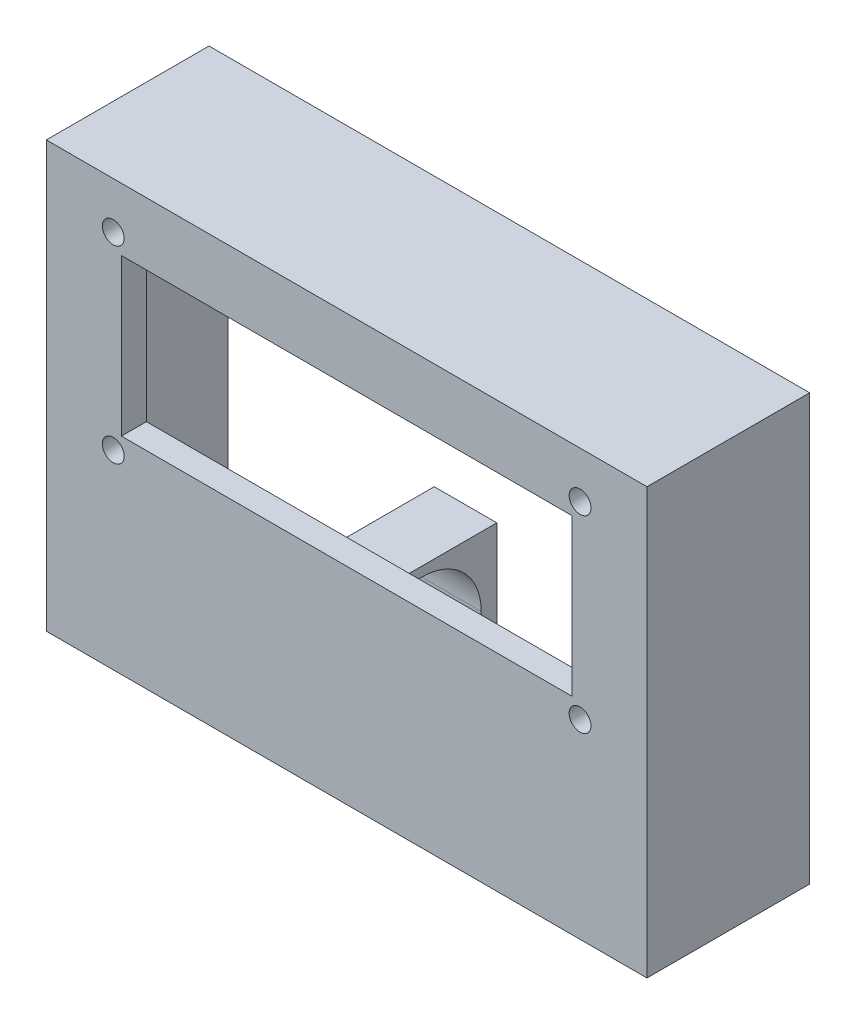
SolidWorks part; units mm, degrees
ref_plane "Plan de face" through (0, 0, 0) normal (0, 0, 1) x (1, 0, 0)
ref_plane "Plan de dessus" through (0, 0, 0) normal (0, 1, 0) x (1, 0, 0)
ref_plane "Plan de droite" through (0, 0, 0) normal (1, 0, 0) x (0, 0, -1)
sketch "Esquisse1" plane through (0, 0, 0) normal (0, 0, 1) x (1, 0, 0)
  line L1 (0, 0) -> (96, 0)
  line L2 (0, 0) -> (0, -68)
  line L3 (0, -68) -> (96, -68)
  line L4 (96, 0) -> (96, -68)
  line L5 (12, -10) -> (84, -10)
  line L6 (12, -10) -> (12, -35)
  line L7 (12, -35) -> (84, -35)
  line L8 (84, -10) -> (84, -35)
  dimension "D1" = 72
  dimension "D2" = 25
  dimension "D3" = 12
  dimension "D4" = 12
  dimension "D5" = 10
  dimension "D6" = 33
extrude "Boss.-Extru.1" add sketch "Esquisse1" along normal blind 4
sketch "Esquisse2" plane through (0, 0, 4) normal (0, 0, 1) x (1, 0, 0)
  line L0 (12, -10) -> (12, -35) construction
  line L2 (84, -35) -> (84, -10) construction
  line L3 (12, -35) -> (84, -35) construction
  line L4 (84, -10) -> (12, -10) construction
  circle A0 centre (85.305, -7.42) radius 1.75
  circle A1 centre (85.305, -37.58) radius 1.75
  circle A2 centre (10.695, -37.58) radius 1.75
  circle A3 centre (10.695, -7.42) radius 1.75
  point P10 (12, -22.5)
  point P13 (84, -22.5)
  point P16 (48, -35)
  point P19 (48, -10)
  dimension "D6" = 3.5
  dimension "D7" = 3.5
  dimension "D8" = 3.5
  dimension "D9" = 3.5
  dimension "D1" = 30.16
  dimension "D2" = 74.61
  dimension "D3" = 74.61
  dimension "D4" = 30.16
  dimension "D5" = 30.16
  dimension "D10" = 15.08
  dimension "D11" = 15.08
  dimension "D12" = 15.08
  dimension "D13" = 15.08
  dimension "D14" = 37.305
  dimension "D15" = 37.305
  dimension "D16" = 37.305
extrude "Enlèv. mat.-Extru.1" cut sketch "Esquisse2" against normal blind 4
sketch "Esquisse3" plane through (0, 0, 0) normal (0, 0, -1) x (-1, 0, 0)
  line L0 (0, -68) -> (-96, -68) construction
  line L1 (-86, -43) -> (-76, -43)
  line L2 (-86, -43) -> (-86, -65)
  line L3 (-86, -65) -> (-76, -65)
  line L4 (-76, -43) -> (-76, -65)
  line L5 (-36, -43) -> (-46, -43)
  line L6 (-36, -43) -> (-36, -65)
  line L7 (-36, -65) -> (-46, -65)
  line L8 (-46, -43) -> (-46, -65)
  line L13 (-96, -68) -> (-96, 0) construction
  point P10 (-81, -65)
  point P11 (-41, -65)
  dimension "D1" = 22
  dimension "D2" = 22
  dimension "D3" = 10
  dimension "D4" = 10
  dimension "D5" = 3
  dimension "D6" = 3
  dimension "D7" = 40
  dimension "D8" = 10
extrude "Boss.-Extru.2" add sketch "Esquisse3" along normal blind 22
sketch "Esquisse4" plane through (86, 0, 0) normal (1, 0, 0) x (0, 0, -1)
  line L0 (0, -68) -> (0, 0) construction
  line L1 (22, -65) -> (0, -65) construction
  line L2 (19.5, -54) -> (19.5, -65)
  line L3 (19.5, -65) -> (0.5, -65)
  line L4 (0.5, -65) -> (0.5, -54)
  circle A0 centre (10, -54) radius 9.5
  line M3 (0, -65) -> (22, -65)
  dimension "D1" = 19
  dimension "D2" = 10
  dimension "D3" = 11
sketch "Esquisse5" plane through (0, 0, 0) normal (0, 0, -1) x (-1, 0, 0)
  line L1 (-96, 0) -> (0, 0)
  line L2 (-96, 0) -> (-96, -68)
  line L3 (-96, -68) -> (0, -68)
  line L4 (0, 0) -> (0, -68)
  line L5 (-93, -3) -> (-3, -3)
  line L6 (-93, -3) -> (-93, -65)
  line L7 (-93, -65) -> (-3, -65)
  line L8 (-3, -3) -> (-3, -65)
  point P10 (0, 0)
  point P11 (-83, -3)
  dimension "D1" = 3
  dimension "D2" = 3
  dimension "D3" = 3
  dimension "D4" = 3
extrude "Boss.-Extru.3" add sketch "Esquisse5" along normal blind 22
extrude "Enlèv. mat.-Extru.3" cut sketch "Esquisse4" against normal blind 54 contours A0 | A0 L4 L2 M3 region at (86, -54, -10) region at (86, -59.5, -19.2805)
